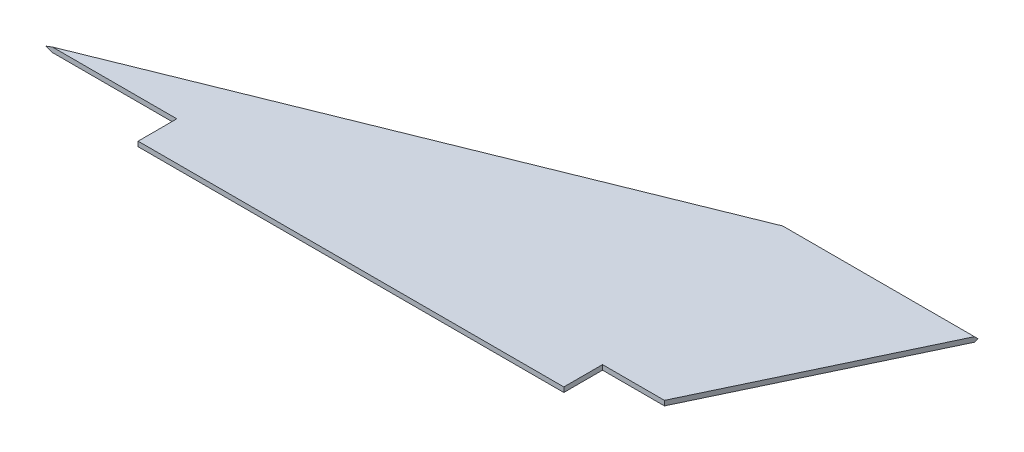
SolidWorks part; units mm, degrees
ref_plane "Front Plane" through (0, 0, 0) normal (0, 0, 1) x (1, 0, 0)
ref_plane "Top Plane" through (0, 0, 0) normal (0, 1, 0) x (1, 0, 0)
ref_plane "Right Plane" through (0, 0, 0) normal (1, 0, 0) x (0, 0, -1)
sketch "Sketch1" plane through (0, 0, 0) normal (0, 1, 0) x (1, 0, 0)
  line L0 (279.4, 25.4) -> (320.04, 25.4)
  line L1 (0, 0) -> (279.4, 0)
  line L2 (0, 0) -> (0, 25.4)
  line L4 (279.4, 0) -> (279.4, 25.4)
  line L5 (0, 25.4) -> (-86.36, 25.4)
  line L6 (-86.36, 25.4) -> (259.4096, 165.1)
  line L7 (259.4096, 165.1) -> (386.4096, 165.1)
  line L8 (386.4096, 165.1) -> (320.04, 25.4)
  line L9 (-86.36, 25.4) -> (-86.36, 176.2647) construction
  dimension "D1" = 279.4
  dimension "D2" = 25.4
  dimension "D3" = 40.64
  dimension "D4" = 406.4
  dimension "D5" = 139.7
  dimension "D6" = 127
  dimension "D8" = 68
extrude "Boss-Extrude1" add sketch "Sketch1" along normal blind 3.175
chamfer "Chamfer1" distance 1.778 angle 45 2 edges at (86.5248, 3.175, -95.25) (86.5248, 0, -95.25)
chamfer "Chamfer2" distance 1.778 angle 45 2 edges at (325.2828, 3.175, -165.1) (325.2828, 0, -165.1)
